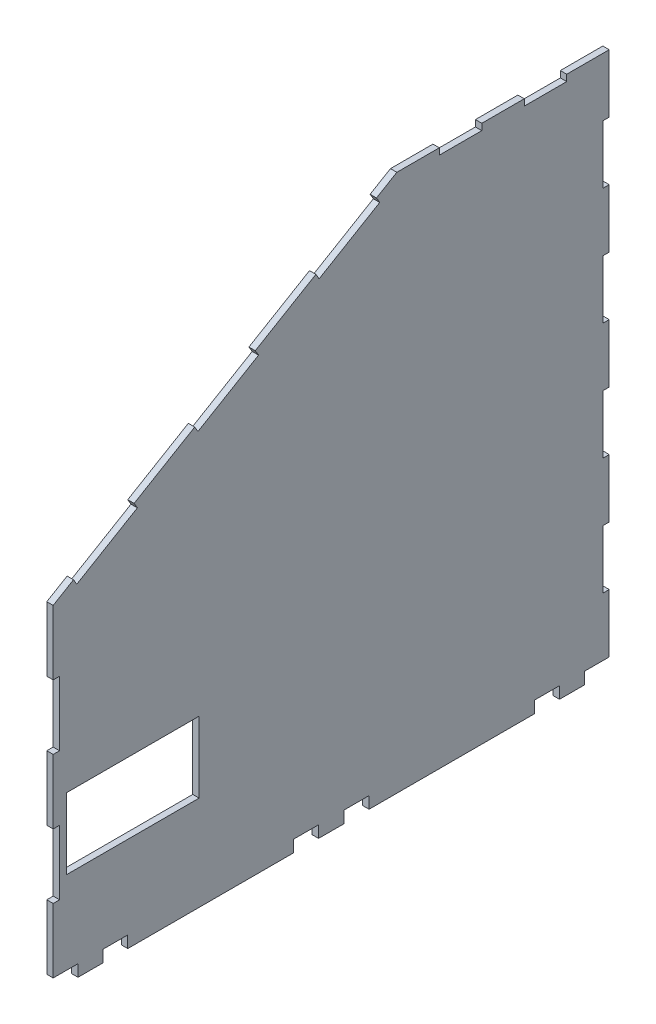
SolidWorks part; units mm, degrees
ref_plane "Ön Düzlem" through (0, 0, 0) normal (0, 0, 1) x (1, 0, 0)
ref_plane "Üst Düzlem" through (0, 0, 0) normal (0, 1, 0) x (1, 0, 0)
ref_plane "Sağ Düzlem" through (0, 0, 0) normal (1, 0, 0) x (0, 0, -1)
sketch "Sketch1" plane through (0, 0, 0) normal (1, 0, 0) x (0, 0, -1)
  line L0 (117.52, 112.5) -> (99.566, 112.5)
  line L6 (117.52, -109.8) -> (117.52, -85.1)
  line L13 (-107.0133, -112.5) -> (-107.0133, -114.8)
  line L14 (-6.4686, 92.2661) -> (-32.0795, 77.122)
  line L17 (27.75, 112.5) -> (19.1423, 107.4101)
  line L18 (-117.52, -109.8) -> (-107.0133, -109.8)
  line L19 (-117.52, -109.8) -> (-117.52, -82.52)
  line L20 (-107.0133, -114.8) -> (-96.5067, -114.8)
  line L21 (-86, -112.5) -> (-86, -114.8)
  line L22 (-114.82, -27.96) -> (-114.82, -0.68)
  line L23 (-117.52, -55.24) -> (-117.52, -27.96)
  line L24 (-96.5067, -114.8) -> (-96.5067, -112.5)
  line L25 (-117.52, -0.68) -> (-117.52, 26.6)
  line L26 (-117.52, -0.68) -> (-114.82, -0.68)
  line L27 (-117.52, -27.96) -> (-114.82, -27.96)
  line L28 (-114.82, -82.52) -> (-114.82, -55.24)
  line L29 (-117.52, -55.24) -> (-114.82, -55.24)
  line L30 (-117.52, -82.52) -> (-114.82, -82.52)
  line L31 (-86, -109.8) -> (-86, -112.5)
  line L32 (-107.0133, -109.8) -> (-107.0133, -112.5)
  line L33 (-96.5067, -109.8) -> (-96.5067, -112.5)
  line L34 (-96.5067, -109.8) -> (-86, -109.8)
  line L35 (-5.3333, -112.5) -> (-5.3333, -114.8)
  line L37 (-16, -112.5) -> (-16, -109.8)
  line L38 (-16, -109.8) -> (-5.3333, -109.8)
  line L39 (-5.3333, -114.8) -> (5.3333, -114.8)
  line L40 (-86, -114.8) -> (-16, -114.8)
  line L41 (5.3333, -109.8) -> (16, -109.8)
  line L42 (-5.3333, -109.8) -> (-5.3333, -112.5)
  line L43 (5.3333, -109.8) -> (5.3333, -112.5)
  line L44 (16, -109.8) -> (16, -112.5)
  line L45 (5.3333, -114.8) -> (5.3333, -112.5)
  line L46 (96.5067, -112.5) -> (96.5067, -114.8)
  line L47 (114.82, -35.7) -> (114.82, -11)
  line L48 (86, -109.8) -> (96.5067, -109.8)
  line L49 (96.5067, -114.8) -> (107.0133, -114.8)
  line L51 (86, -109.8) -> (86, -112.5)
  line L52 (96.5067, -109.8) -> (96.5067, -112.5)
  line L53 (107.0133, -109.8) -> (107.0133, -112.5)
  line L55 (107.0133, -109.8) -> (117.52, -109.8)
  line L56 (117.52, -60.4) -> (117.52, -35.7)
  line L57 (114.82, 13.7) -> (114.82, 38.4)
  line L58 (117.52, -11) -> (117.52, 13.7)
  line L59 (114.82, 63.1) -> (114.82, 87.8)
  line L60 (117.52, 38.4) -> (117.52, 63.1)
  line L61 (107.0133, -112.5) -> (107.0133, -114.8)
  line L62 (117.52, 87.8) -> (117.52, 112.5)
  line L63 (114.82, -85.1) -> (114.82, -60.4)
  line L64 (117.52, -85.1) -> (114.82, -85.1)
  line L65 (117.52, 13.7) -> (114.82, 13.7)
  line L66 (117.52, 87.8) -> (114.82, 87.8)
  line L67 (117.52, 63.1) -> (114.82, 63.1)
  line L68 (117.52, 38.4) -> (114.82, 38.4)
  line L69 (117.52, -11) -> (114.82, -11)
  line L70 (117.52, -35.7) -> (114.82, -35.7)
  line L71 (117.52, -60.4) -> (114.82, -60.4)
  line L72 (-57.6905, 61.978) -> (-83.3014, 46.8339)
  line L73 (-5.0944, 89.942) -> (-6.4686, 92.2661)
  line L74 (-107.538, 29.3658) -> (-81.9271, 44.5098)
  line L75 (-16, -114.8) -> (-16, -112.5)
  line L76 (99.566, 109.8) -> (81.612, 109.8)
  line L77 (16, -112.5) -> (16, -114.8)
  line L78 (63.658, 109.8) -> (45.704, 109.8)
  line L79 (-108.9123, 31.6899) -> (-117.52, 26.6)
  line L80 (45.704, 109.8) -> (45.704, 112.5)
  line L81 (63.658, 109.8) -> (63.658, 112.5)
  line L82 (81.612, 109.8) -> (81.612, 112.5)
  line L83 (99.566, 109.8) -> (99.566, 112.5)
  line L84 (16, -114.8) -> (86, -114.8)
  line L85 (86, -114.8) -> (86, -112.5)
  line L87 (-108.9123, 31.6899) -> (-107.538, 29.3658)
  line L88 (19.1423, 107.4101) -> (20.5165, 105.086)
  line L89 (-56.3162, 59.6539) -> (-30.7053, 74.7979)
  line L91 (-5.0944, 89.942) -> (20.5165, 105.086)
  line L92 (-30.7053, 74.7979) -> (-32.0795, 77.122)
  line L93 (-56.3162, 59.6539) -> (-57.6905, 61.978)
  line L94 (-81.9271, 44.5098) -> (-83.3014, 46.8339)
  line L95 (45.704, 112.5) -> (27.75, 112.5)
  line L97 (81.612, 112.5) -> (63.658, 112.5)
  line L103 (-114.82, -41.8) -> (-111.82, -41.8)
  line L105 (-111.82, -74.8) -> (-111.82, -44.8)
  line L109 (-111.82, -44.8) -> (-55.82, -44.8)
  line L112 (-55.82, -44.8) -> (-55.82, -74.8)
  line L114 (-55.82, -74.8) -> (-111.82, -74.8)
  point P0 (0, 0)
extrude "Boss-Extrude1" add sketch "Sketch1" along normal blind 2.7 contours L82 L97 L81 L78 L80 L95 L17 L88 L91 L73 L14 L92 L89 L93 L72 L94 L74 L87 L79 L25 L26 L22 L27 L23 L29 L28 L30 L19 L18 L32 L33 L34 L31 L37 L38 L42 L43 L41 L44 L51 L48 L52 L53 region at (0, -10.5805, -12.6398)
ref_plane "Plane1" through (2.7, 112.5, -27.75) normal (0, -0.509, 0.8608) x (1, 0, 0)
sketch "Sketch2" plane through (2.7, 112.5, -27.75) normal (0, -0.509, 0.8608) x (1, 0, 0)
